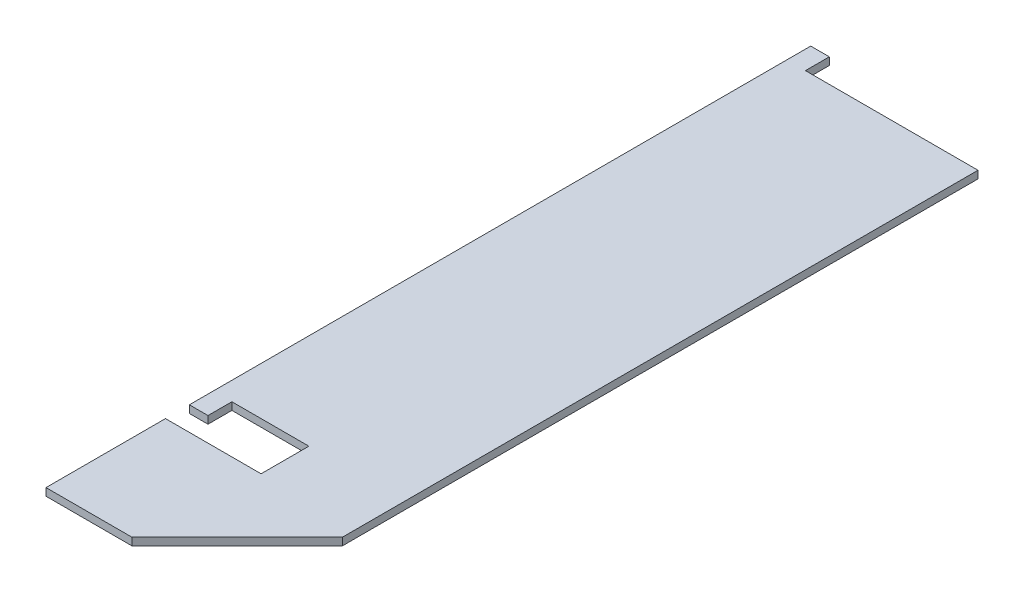
SolidWorks part; units mm, degrees
ref_plane "Front Plane" through (0, 0, 0) normal (0, 0, 1) x (1, 0, 0)
ref_plane "Top Plane" through (0, 0, 0) normal (0, 1, 0) x (1, 0, 0)
ref_plane "Right Plane" through (0, 0, 0) normal (1, 0, 0) x (0, 0, -1)
sketch "Sketch1" plane through (0, 0, 0) normal (0, 1, 0) x (1, 0, 0)
  line L0 (0, -38.1) -> (0, -44.45)
  line L1 (-12.7, -38.1) -> (0, -38.1)
  line L2 (-12.7, -38.1) -> (-12.7, 38.1)
  line L3 (-12.7, 38.1) -> (12.7, 38.1)
  line L4 (12.7, -38.1) -> (12.7, 38.1)
  line L5 (-12.7, -38.1) -> (12.7, 38.1) construction
  line L6 (-12.7, 38.1) -> (12.7, -38.1) construction
  line L7 (0, -44.45) -> (-12.7, -44.45)
  line L8 (-12.7, -44.45) -> (-12.7, -60.325)
  line L9 (-12.7, -60.325) -> (12.7, -60.325)
  line L10 (12.7, -60.325) -> (12.7, -38.1)
  point P0 (0, 0)
  dimension "D1" = 25.4
  dimension "D2" = 76.2
  dimension "D3" = 12.7
  dimension "D4" = 6.35
  dimension "D5" = 15.875
extrude "Boss-Extrude1" add sketch "Sketch1" along normal blind 1.0008
sketch "Sketch2" plane through (0, 0, 38.1) normal (0, 0, 1) x (1, 0, 0)
  line L0 (-12.7, 1.0008) -> (0, 1.0008) construction
  line L1 (-12.7, 0) -> (-10.2279, 0)
  line L2 (-12.7, 0) -> (-12.7, 1.0008)
  line L3 (-12.7, 1.0008) -> (-10.2279, 1.0008)
  line L4 (-10.2279, 0) -> (-10.2279, 1.0008)
  dimension "D1" = 2.667
extrude "Boss-Extrude2" add sketch "Sketch2" along normal blind 3.175
mirror "Mirror1" about plane through (0, 0, 0) normal (0, 0, 1) of "Boss-Extrude2"
chamfer "Chamfer2" distance 13.97 angle 45 1 edges at (12.7, 0.5004, 60.325)
equation "\"looseTol\"= 0.02in"
equation "\"tightTol\"= 0.005in"
equation "\"normTol\"= 0.01in"
equation "\"D1@Sketch2\"=0.125000in-\"looseTol\""
